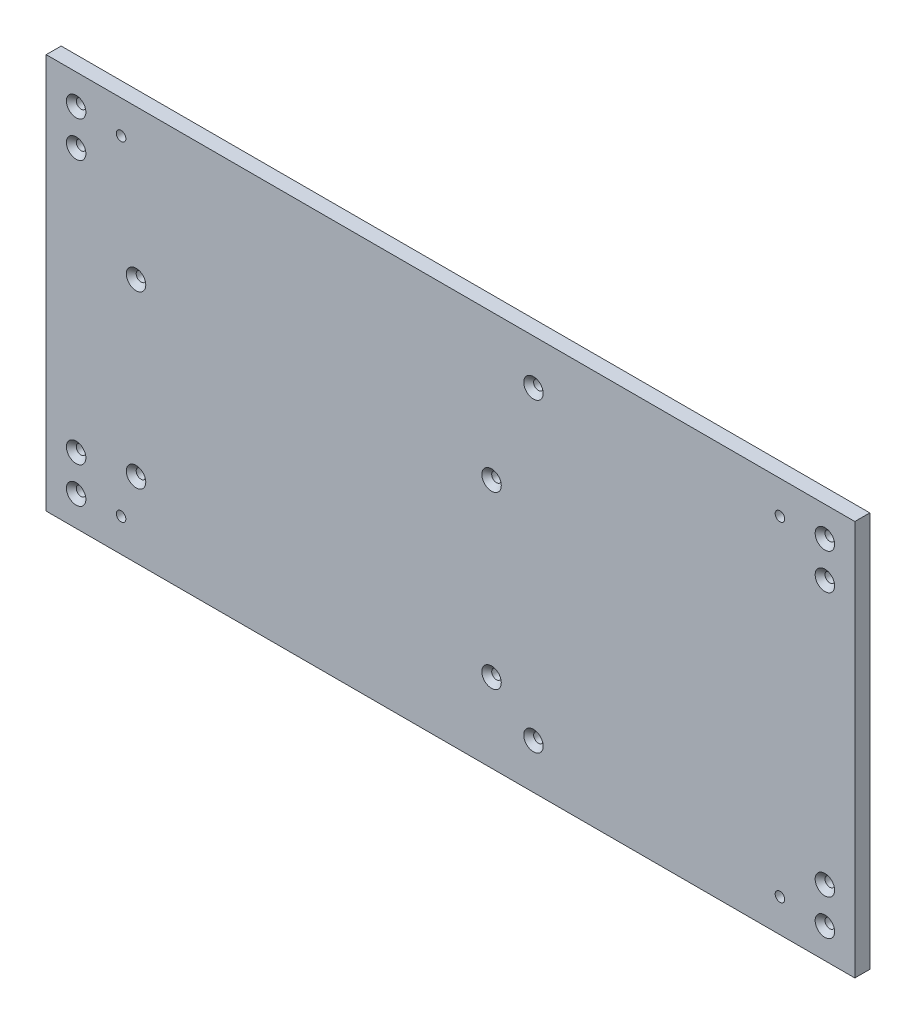
SolidWorks part; units mm, degrees
material "Polycarbonate (PC)"
ref_plane "Front Plane" through (0, 0, 0) normal (0, 0, 1) x (1, 0, 0)
ref_plane "Top Plane" through (0, 0, 0) normal (0, 1, 0) x (1, 0, 0)
ref_plane "Right Plane" through (0, 0, 0) normal (1, 0, 0) x (0, 0, -1)
sketch "Sketch1" plane through (0, 0, 0) normal (0, 0, 1) x (1, 0, 0)
  line L1 (135, -66) -> (-135, -66)
  line L2 (135, -66) -> (135, 66)
  line L3 (135, 66) -> (-135, 66)
  line L4 (-135, -66) -> (-135, 66)
  line L5 (135, -66) -> (-135, 66) construction
  line L6 (135, 66) -> (-135, -66) construction
  point P0 (0, 0)
  dimension "D1" = 270
  dimension "D2" = 132
extrude "Sheet" add sketch "Sketch1" along normal mid plane 5 contours L4 L1 L2 L3 region at (0, 0, 0)
hole_wizard "Ø3.2 (3.2) WallMountHoles" positions "Sketch6" profile "Sketch7" hole size "Ø3.2" standard "ANSI Metric" end condition through all
sketch "Sketch6" plane through (0, 0, 2.5) normal (0, 0, 1) x (1, 0, 0)
  line L0 (135, 66) -> (-135, 66) construction
  line L1 (-135, -66) -> (-135, 66) construction
  line L4 (135, -66) -> (135, 66) construction
  line L5 (135, -66) -> (-135, -66) construction
  point P0 (-125, 56)
  point P2 (-125, 44)
  point P4 (-125, -44)
  point P6 (-125, -56)
  point P8 (125, -56)
  point P10 (125, -44)
  point P12 (125, 44)
  point P14 (125, 56)
  point P45 (27.7, -51)
  point P47 (27.7, 51)
  point P50 (0, 0)
  dimension "D1" = 10
  dimension "D2" = 22
  dimension "D4" = 10
  dimension "D3" = 10
  dimension "D5" = 10
  dimension "D6" = 22
  dimension "D7" = 15
  dimension "D8" = 15
  dimension "D9" = 162.7
sketch "Sketch7" plane through (-125, 56, 2.5) normal (1, 0, 0) x (0, -1, 0)
  line L0 (0, 0) -> (0, 5)
  line L1 (0, 5) -> (1.6, 5)
  line L2 (1.6, 5) -> (1.6, 1.65)
  line L3 (1.6, 1.65) -> (3.25, 0)
  line L5 (3.25, 0) -> (0, 0)
  line L6 (-1.6, 1.65) -> (-3.25, 0) construction
  line L11 (0, -6.35) -> (0, 107.95) construction
  dimension "Thru Hole Dia." = 3.2
  dimension "Thru Hole Depth" = 5
  dimension "Near C'Sink Dia." = 6.5
  dimension "Near C'Sink Angle" = 90
hole_wizard "Ø3.2 (3.2) FeetMountHoles" positions "Sketch9" profile "Sketch8" hole size "Ø3.2" standard "ANSI Metric" end condition through all
sketch "Sketch9" plane through (0, 0, 2.5) normal (0, 0, 1) x (1, 0, 0)
  line L0 (135, -66) -> (-135, -66) construction
  line L1 (135, -66) -> (135, 66) construction
  point P0 (110, 55)
  point P2 (-110, 55)
  point P4 (-110, -55)
  point P6 (110, -55)
  dimension "D1" = 220
  dimension "D2" = 110
  dimension "D3" = 11
  dimension "D4" = 25
sketch "Sketch8" plane through (110, 55, 2.5) normal (1, 0, 0) x (0, -1, 0)
  line L0 (0, 0) -> (0, 5)
  line L1 (0, 5) -> (1.6, 5)
  line L2 (1.6, 5) -> (1.6, 0)
  line L5 (1.6, 0) -> (0, 0)
  line L11 (0, -6.35) -> (0, 107.95) construction
  dimension "Thru Hole Dia." = 3.2
  dimension "Thru Hole Depth" = 5
hole_wizard "Ø3.2 (3.2) PSUHoles" positions "Sketch10" profile "Sketch11" hole size "Ø3.2" standard "ANSI Metric" end condition through all
sketch "Sketch10" plane through (0, 0, 2.5) normal (0, 0, 1) x (1, 0, 0)
  line L2 (-135, -66) -> (-135, 66) construction
  line L3 (135, -66) -> (-135, -66) construction
  line L4 (135, 66) -> (-135, 66) construction
  point P0 (13.7, -39.65)
  point P2 (-105, 16)
  point P11 (13.7, 17.35)
  point P13 (-105, -41)
  point P16 (0, 0)
  point P17 (0, 0)
  point P18 (-90, -49.65)
  point P19 (-90, -49.65)
  point P20 (28.7, -51)
  point P21 (-90, -30.7693)
  point P22 (28.7, 42.6012)
  point P23 (28.7, -24.3299)
  point P24 (-90, 27.4278)
  point P25 (-90, -39.7413)
  point P26 (-90, 18.5131)
  point P27 (-90, -46.0525)
  point P28 (-90, 18.3167)
  dimension "D1" = 1.35
  dimension "D2" = 1.35
  dimension "D3" = 25
  dimension "D4" = 30
  dimension "D5" = 118.7
  dimension "D6" = 50
sketch "Sketch11" plane through (13.7, -39.65, 2.5) normal (1, 0, 0) x (0, -1, 0)
  line L0 (0, 0) -> (0, 5)
  line L1 (0, 5) -> (1.6, 5)
  line L2 (1.6, 5) -> (1.6, 1.65)
  line L3 (1.6, 1.65) -> (3.25, 0)
  line L5 (3.25, 0) -> (0, 0)
  line L6 (-1.6, 1.65) -> (-3.25, 0) construction
  line L11 (0, -6.35) -> (0, 107.95) construction
  dimension "Thru Hole Dia." = 3.2
  dimension "Thru Hole Depth" = 5
  dimension "Near C'Sink Dia." = 6.5
  dimension "Near C'Sink Angle" = 90
equation "\"D3@Sketch6\"=\"D4@Sketch6\""
equation "\"D5@Sketch6\"=\"D1@Sketch6\""
equation "\"D6@Sketch6\"=\"D2@Sketch6\""
equation "\"D3@Sketch9\"=(\"D2@Sketch1\"-\"D2@Sketch9\")/2"
equation "\"D4@Sketch9\"=(\"D1@Sketch1\"-\"D1@Sketch9\")/2"
equation "\"D7@Sketch6\"=\"D8@Sketch6\""
